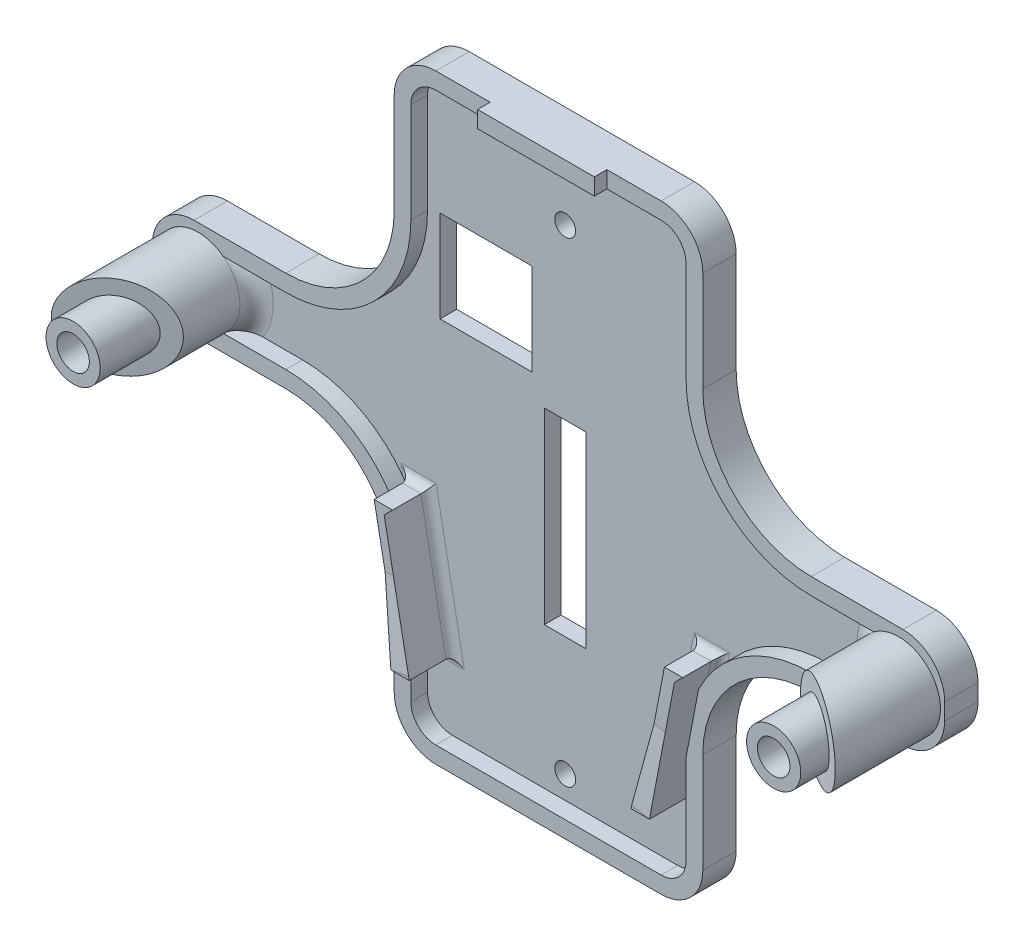
SolidWorks part; units mm, degrees
ref_plane "Front Plane" through (0, 0, 0) normal (0, 0, 1) x (1, 0, 0)
ref_plane "Top Plane" through (0, 0, 0) normal (0, 1, 0) x (1, 0, 0)
ref_plane "Right Plane" through (0, 0, 0) normal (1, 0, 0) x (0, 0, -1)
ref_plane "Plane1" through (0, 0, -5.5) normal (0, 0, 1) x (1, 0, 0)
sketch "Sketch1" plane through (0, 0, -5.5) normal (0, 0, 1) x (1, 0, 0)
  line L0 (47.5, -36) -> (47.5, 36)
  line L1 (47.5, 36) -> (-47.5, 36)
  line L2 (-47.5, 36) -> (-47.5, -36)
  line L3 (-47.5, -36) -> (47.5, -36)
extrude "Boss-Extrude1" add sketch "Sketch1" against normal blind 4
sketch "Sketch2" plane through (0, 0, -5.5) normal (0, 0, 1) x (1, 0, 0)
  line L0 (-7, 36) -> (7, 36)
  line L1 (7, 36) -> (7, 34)
  line L2 (7, 34) -> (-7, 34)
  line L3 (-7, 34) -> (-7, 36)
extrude "Boss-Extrude2" add sketch "Sketch2" along normal blind 1.5
ref_plane "Plane2" through (8.8675, 0, -15.1689) normal (-0.5047, 0, 0.8633) x (0, -1, 0)
sketch "Sketch4" plane through (0, 0, -5.5) normal (0, 0, 1) x (1, 0, 0)
  circle A0 centre (42, 0) radius 5
extrude "Boss-Extrude3" add sketch "Sketch4" along normal up to surface up to plane "Plane2"
ref_plane "Plane3" through (-8.8675, 0, -15.1689) normal (0.5047, 0, 0.8633) x (0, 1, 0)
sketch "Sketch6" plane through (0, 0, -5.5) normal (0, 0, 1) x (1, 0, 0)
  circle A0 centre (-42, 0) radius 5
extrude "Boss-Extrude4" add sketch "Sketch6" along normal up to surface up to plane "Plane3"
sketch "Sketch7" plane through (0, 0, -5.5) normal (0, 0, 1) x (1, 0, 0)
  line L0 (16.5, 34) -> (-16.5, 34)
  line L1 (-16.5, 34) -> (-16.5, 4)
  line L2 (-16.5, 4) -> (-39, 4)
  line L3 (-39, -4) -> (-31.5, -4)
  line L4 (-17.9858, -12.4911) -> (-18.5, -9.8)
  line L5 (-18.5, -9.8) -> (-16.3006, -9.8)
  line L6 (-16.3006, -9.8) -> (-13.3, -25.5)
  line L7 (-13.3, -25.5) -> (-15.5, -25.5)
  line L8 (-15.5, -25.5) -> (-16.5, -20.2667)
  line L9 (-16.5, -20.2667) -> (-16.5, -34)
  line L10 (-16.5, -34) -> (16.5, -34)
  line L11 (16.5, -34) -> (16.5, -20.2667)
  line L12 (16.5, -20.2667) -> (15.5, -25.5)
  line L13 (15.5, -25.5) -> (13.3, -25.5)
  line L14 (13.3, -25.5) -> (16.3006, -9.8)
  line L15 (16.3006, -9.8) -> (18.5, -9.8)
  line L16 (18.5, -9.8) -> (17.9858, -12.4911)
  line L17 (31.5, -4) -> (39, -4)
  line L18 (39, 4) -> (16.5, 4)
  line L19 (16.5, 4) -> (16.5, 34)
  arc A0 (-39, 4) -> (-39, -4) centre (-42, 0) cw
  arc A1 (-31.5, -4) -> (-17.9858, -12.4911) centre (-31.5, -19) cw
  arc A2 (17.9858, -12.4911) -> (31.5, -4) centre (31.5, -19) cw
  arc A3 (39, -4) -> (39, 4) centre (42, 0) cw
extrude "Cut-Extrude1" cut sketch "Sketch7" against normal blind 2
sketch "Sketch8" plane through (0, 0, -5.5) normal (0, 0, 1) x (1, 0, 0)
  line L0 (13.3, -25.5) -> (16.3006, -9.8)
  line L1 (16.3006, -9.8) -> (18.5, -9.8)
  line L2 (18.5, -9.8) -> (15.5, -25.5)
  line L3 (15.5, -25.5) -> (13.3, -25.5)
extrude "Boss-Extrude5" add sketch "Sketch8" along normal blind 3.4
sketch "Sketch9" plane through (0, 0, -5.5) normal (0, 0, 1) x (1, 0, 0)
  line L0 (-16.3006, -9.8) -> (-13.3, -25.5)
  line L1 (-13.3, -25.5) -> (-15.5, -25.5)
  line L2 (-15.5, -25.5) -> (-18.5, -9.8)
  line L3 (-18.5, -9.8) -> (-16.3006, -9.8)
extrude "Boss-Extrude6" add sketch "Sketch9" along normal blind 3.4
sketch "Sketch10" plane through (0, 0, -9.5) normal (0, 0, -1) x (-1, 0, 0)
  line L0 (-47.5, 6) -> (-18.5, 6)
  line L1 (-18.5, 6) -> (-18.5, 36)
  line L2 (-18.5, 36) -> (-47.5, 36)
  line L3 (-47.5, 36) -> (-47.5, 6)
extrude "Cut-Extrude2" cut sketch "Sketch10" against normal through all
sketch "Sketch11" plane through (0, 0, -9.5) normal (0, 0, -1) x (-1, 0, 0)
  line L0 (47.5, 36) -> (18.5, 36)
  line L1 (18.5, 36) -> (18.5, 6)
  line L2 (18.5, 6) -> (47.5, 6)
  line L3 (47.5, 6) -> (47.5, 36)
extrude "Cut-Extrude3" cut sketch "Sketch11" against normal through all
sketch "Sketch12" plane through (0, 0, -2.1) normal (0, 0, 1) x (1, 0, 0)
  line L0 (-17.1862, -16.6756) -> (-15.0643, -16.2701)
  line L1 (-15.0643, -16.2701) -> (-16.3006, -9.8)
  line L2 (-16.3006, -9.8) -> (-18.5, -9.8)
  line L3 (-18.5, -9.8) -> (-17.1862, -16.6756)
extrude "Cut-Extrude4" cut sketch "Sketch12" against normal blind 1
sketch "Sketch13" plane through (0, 0, -9.5) normal (0, 0, -1) x (-1, 0, 0)
  line L0 (47.5, -36) -> (47.5, -6)
  line L1 (47.5, -6) -> (31.5, -6)
  line L2 (18.5, -19) -> (18.5, -36)
  line L3 (18.5, -36) -> (47.5, -36)
  arc A0 (31.5, -6) -> (18.5, -19) centre (31.5, -19) ccw
extrude "Cut-Extrude5" cut sketch "Sketch13" against normal through all
sketch "Sketch14" plane through (0, 0, -2.1) normal (0, 0, 1) x (1, 0, 0)
  line L0 (16.3004, -9.8) -> (15.064, -16.2701)
  line L1 (15.064, -16.2701) -> (17.1859, -16.6756)
  line L2 (17.1859, -16.6756) -> (18.4998, -9.8)
  line L3 (18.4998, -9.8) -> (16.3004, -9.8)
extrude "Cut-Extrude6" cut sketch "Sketch14" against normal blind 1
sketch "Sketch15" plane through (0, 0, -9.5) normal (0, 0, -1) x (-1, 0, 0)
  line L0 (-47.5, -36) -> (-18.5, -36)
  line L1 (-18.5, -36) -> (-18.5, -19)
  line L2 (-31.5, -6) -> (-47.5, -6)
  line L3 (-47.5, -6) -> (-47.5, -36)
  arc A0 (-18.5, -19) -> (-31.5, -6) centre (-31.5, -19) ccw
extrude "Cut-Extrude7" cut sketch "Sketch15" against normal through all
sketch "Sketch16" plane through (0, 0, -7.5) normal (0, 0, 1) x (1, 0, 0)
  line L0 (2.5, 5.5) -> (-2.5, 5.5)
  line L1 (-2.5, 5.5) -> (-2.5, -17)
  line L2 (-2.5, -17) -> (2.5, -17)
  line L3 (2.5, -17) -> (2.5, 5.5)
extrude "Cut-Extrude8" cut sketch "Sketch16" against normal through all
sketch "Sketch17" plane through (0, 0, -9.5) normal (0, 0, -1) x (-1, 0, 0)
  line L0 (4, 8.5) -> (15, 8.5)
  line L1 (15, 8.5) -> (15, 19.5)
  line L2 (15, 19.5) -> (4, 19.5)
  line L3 (4, 19.5) -> (4, 8.5)
extrude "Cut-Extrude9" cut sketch "Sketch17" against normal through all
draft "Draft1" type of draft neutral plane draft angle 83.649 faces to draft 1 face at (-16.1252, -16.4729, -2.6) neutral plane through (0, 0, -3.1) neutral plane normal (0, 0, 1) parameters "D1"=83.649
draft "Draft2" type of draft neutral plane draft angle 83.649 faces to draft 1 face at (16.125, -16.4728, -2.6) neutral plane through (0, 0, -3.1) neutral plane normal (0, 0, 1) parameters "D1"=83.649
sketch "Sketch18" plane through (0, 0, 0) normal (0, 1, 0) x (1, 0, 0)
  line L0 (-45.25, -9.5) -> (-42, -9.5)
  line L1 (-42, -9.5) -> (-42, -2.3)
  line L2 (-42, -2.3) -> (-45.25, -2.3)
  line L3 (-45.25, -2.3) -> (-45.25, -9.5)
  line L4 (-42, -9.5) -> (-42, -2.3) construction
revolve "Revolve1" add sketch "Sketch18" angle 360 about L4 reverse direction yes
sketch "Sketch19" plane through (0, 0, 0) normal (0, 1, 0) x (1, 0, 0)
  line L0 (38.75, -9.5) -> (42, -9.5)
  line L1 (42, -9.5) -> (42, -2.3)
  line L2 (42, -2.3) -> (38.75, -2.3)
  line L3 (38.75, -2.3) -> (38.75, -9.5)
  line L4 (42, -9.5) -> (42, -2.3) construction
revolve "Revolve2" add sketch "Sketch19" angle 360 about L4 reverse direction yes
hole_wizard "Hole1" positions "Sketch21" profile "Sketch20" legacy
sketch "Sketch21" plane through (0, 0, -7.5) normal (0, 0, 1) x (1, 0, 0)
  point P0 (0, -31.25)
sketch "Sketch20" plane through (0, -31.25, -7.5) normal (1, 0, 0) x (0, -1, 0)
  line L0 (0, 0) -> (0, 2)
  line L1 (0, 2) -> (1.25, 2)
  line L2 (1.25, 2) -> (1.25, 0)
  line L3 (1.25, 0) -> (0, 0)
  line L4 (0, 110) -> (0, -10) construction
  dimension "Diameter" = 2.5
  dimension "Depth" = 2
hole_wizard "Hole2" positions "Sketch23" profile "Sketch22" legacy
sketch "Sketch23" plane through (0, 0, -7.5) normal (0, 0, 1) x (1, 0, 0)
  point P0 (0, 25.75)
sketch "Sketch22" plane through (0, 25.75, -7.5) normal (1, 0, 0) x (0, -1, 0)
  line L0 (0, 0) -> (0, 2)
  line L1 (0, 2) -> (1.25, 2)
  line L2 (1.25, 2) -> (1.25, 0)
  line L3 (1.25, 0) -> (0, 0)
  line L4 (0, 110) -> (0, -10) construction
  dimension "Diameter" = 2.5
  dimension "Depth" = 2
hole_wizard "Hole3" positions "Sketch25" profile "Sketch24" legacy
sketch "Sketch25" plane through (0, 0, -9.5) normal (0, 0, -1) x (-1, 0, 0)
  point P0 (42, 0)
sketch "Sketch24" plane through (-42, 0, -9.5) normal (1, 0, 0) x (0, 1, 0)
  line L0 (0, 0) -> (0, 19)
  line L1 (0, 19) -> (1.95, 19)
  line L2 (1.95, 19) -> (1.95, 9.5)
  line L3 (1.95, 9.5) -> (3.75, 9.5)
  line L4 (3.75, 9.5) -> (3.75, 0)
  line L5 (3.75, 0) -> (0, 0)
  line L6 (0, 110) -> (0, -10) construction
  dimension "Diameter" = 3.9
  dimension "Depth" = 19
  dimension "C-Bore Diameter" = 7.5
  dimension "C-Bore Depth" = 9.5
hole_wizard "Hole4" positions "Sketch27" profile "Sketch26" legacy
sketch "Sketch27" plane through (0, 0, -9.5) normal (0, 0, -1) x (-1, 0, 0)
  point P0 (-42, 0)
sketch "Sketch26" plane through (42, 0, -9.5) normal (1, 0, 0) x (0, 1, 0)
  line L0 (0, 0) -> (0, 19)
  line L1 (0, 19) -> (1.95, 19)
  line L2 (1.95, 19) -> (1.95, 9.5)
  line L3 (1.95, 9.5) -> (3.75, 9.5)
  line L4 (3.75, 9.5) -> (3.75, 0)
  line L5 (3.75, 0) -> (0, 0)
  line L6 (0, 110) -> (0, -10) construction
  dimension "Diameter" = 3.9
  dimension "Depth" = 19
  dimension "C-Bore Diameter" = 7.5
  dimension "C-Bore Depth" = 9.5
fillet "Fillet1" radius 1 5 edges at (18.2429, -11.1456, -7.5) (17.4003, -9.8, -7.5) (16, -22.8833, -7.5) (14.8003, -17.65, -7.5) (14.4, -25.5, -7.5)
fillet "Fillet2" radius 1 5 edges at (-16, -22.8833, -7.5) (-14.4, -25.5, -7.5) (-14.8003, -17.65, -7.5) (-17.4003, -9.8, -7.5) (-18.2429, -11.1456, -7.5)
fillet "Fillet3" radius 2 1 edges at (-37, 0, -7.5) tangent propagation no
fillet "Fillet4" radius 2 1 edges at (37, 0, -7.5) tangent propagation no
fillet "Fillet5" radius 3 1 edges at (-16.5, 34, -6.5) tangent propagation no
fillet "Fillet6" radius 3 1 edges at (16.5, 34, -6.5) tangent propagation no
fillet "Fillet7" radius 3 1 edges at (-16.5, -34, -6.5) tangent propagation no
fillet "Fillet8" radius 3 1 edges at (16.5, -34, -6.5) tangent propagation no
fillet "Fillet9" radius 5 1 edges at (-18.5, 36, -7.5) tangent propagation no
fillet "Fillet10" radius 5 1 edges at (-47.5, -6, -7.5) tangent propagation no
fillet "Fillet11" radius 5 1 edges at (-47.5, 6, -7.5) tangent propagation no
fillet "Fillet12" radius 5 1 edges at (18.5, -36, -7.5) tangent propagation no
fillet "Fillet13" radius 5 1 edges at (47.5, 6, -7.5) tangent propagation no
fillet "Fillet14" radius 5 1 edges at (18.5, 36, -7.5) tangent propagation no
fillet "Fillet15" radius 5 1 edges at (-18.5, -36, -7.5) tangent propagation no
fillet "Fillet16" radius 5 1 edges at (47.5, -6, -7.5) tangent propagation no
fillet "Fillet17" radius 13 1 edges at (-18.5, 6, -7.5) tangent propagation no
fillet "Fillet18" radius 13 1 edges at (18.5, 6, -7.5) tangent propagation no
fillet "Fillet19" radius 15 1 edges at (-16.5, 4, -6.5) tangent propagation no
fillet "Fillet20" radius 15 1 edges at (16.5, 4, -6.5) tangent propagation no
